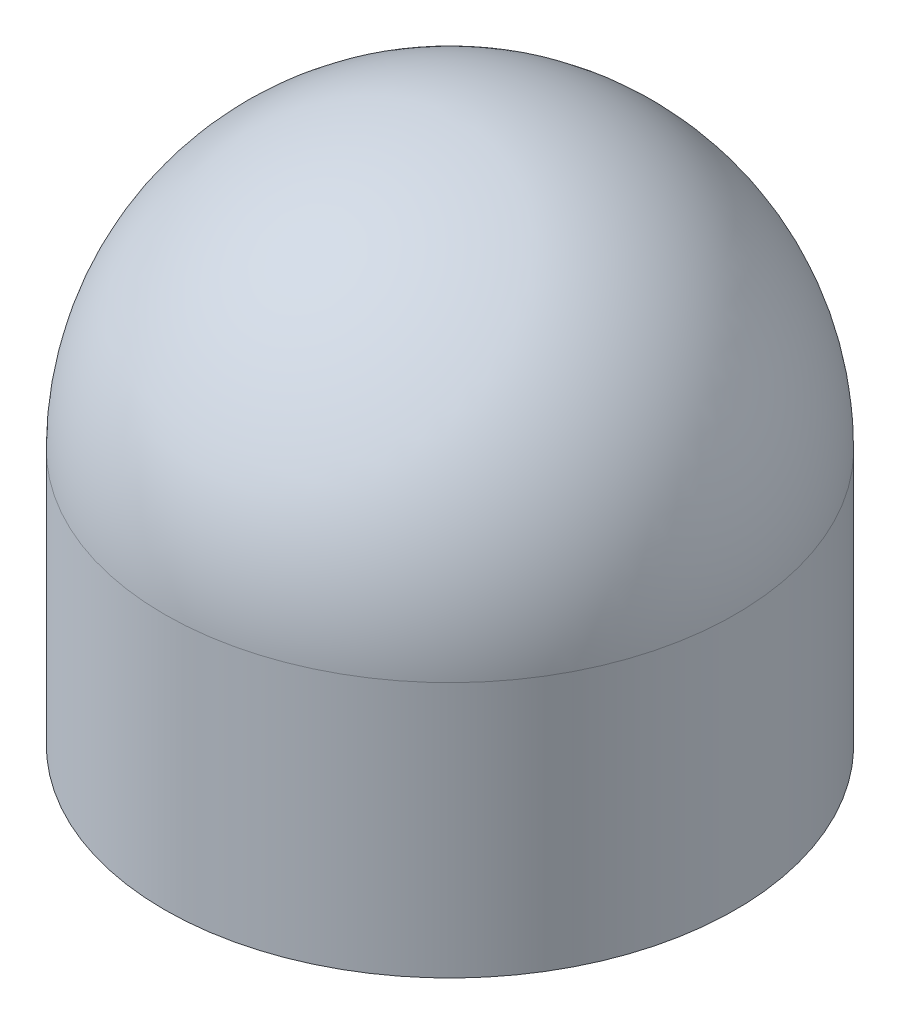
SolidWorks part; units mm, degrees
ref_plane "Front Plane" through (0, 0, 0) normal (0, 0, 1) x (1, 0, 0)
ref_plane "Top Plane" through (0, 0, 0) normal (0, 1, 0) x (1, 0, 0)
ref_plane "Right Plane" through (0, 0, 0) normal (1, 0, 0) x (0, 0, -1)
sketch "Sketch1" plane through (0, 0, 0) normal (0, 1, 0) x (1, 0, 0)
  circle A0 centre (0, 0) radius 5
  dimension "D1" = 10
extrude "Boss-Extrude1" add sketch "Sketch1" along normal blind 9.48
fillet "Fillet1" radius 5 1 edges at (0, 9.48, 5)
sketch "Sketch2" plane through (0, 0, 0) normal (0, -1, 0) x (1, 0, 0)
  circle A0 centre (0, 0) radius 1.75
  dimension "D1" = 3.5
extrude "Cut-Extrude1" cut sketch "Sketch2" against normal blind 4
